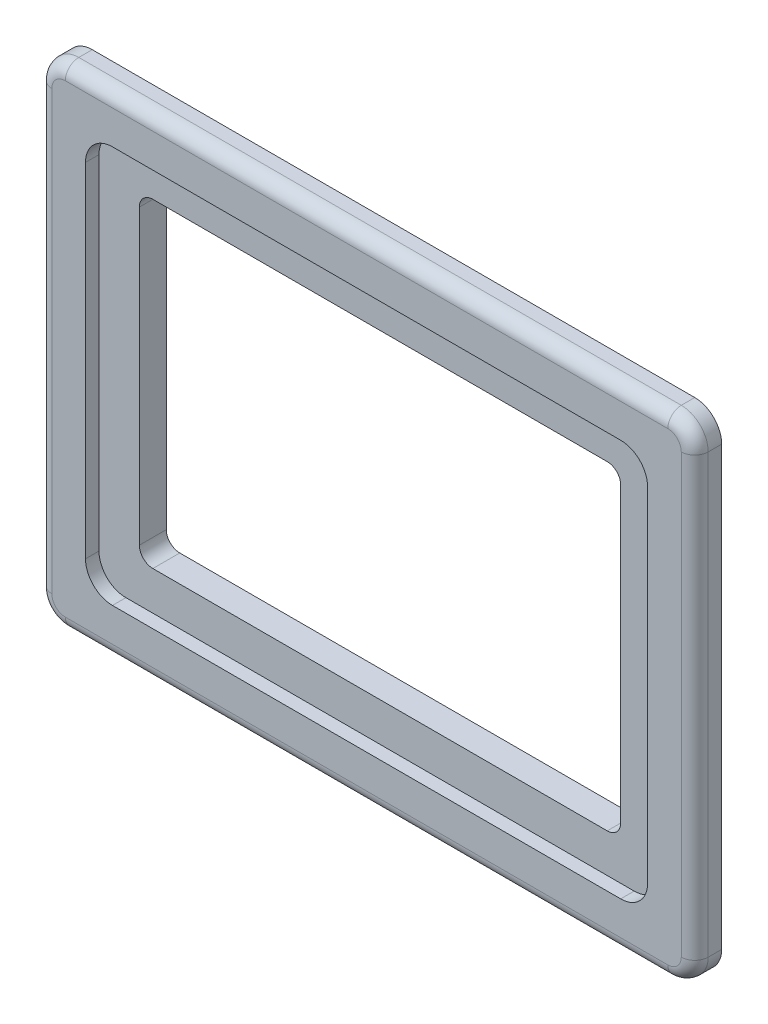
SolidWorks part; units mm, degrees
material "ABS"
ref_plane "Front Plane" through (0, 0, 0) normal (0, 0, 1) x (1, 0, 0)
ref_plane "Top Plane" through (0, 0, 0) normal (0, 1, 0) x (1, 0, 0)
ref_plane "Right Plane" through (0, 0, 0) normal (1, 0, 0) x (0, 0, -1)
sketch "Sketch1" plane through (0, 0, 0) normal (0, 0, 1) x (1, 0, 0)
  line L1 (-154.7812, -115.8875) -> (154.7812, -115.8875)
  line L2 (-154.7812, -115.8875) -> (-154.7812, 115.8875)
  line L3 (-154.7812, 115.8875) -> (154.7812, 115.8875)
  line L4 (154.7812, -115.8875) -> (154.7812, 115.8875)
  line L5 (-154.7812, -115.8875) -> (154.7812, 115.8875) construction
  line L6 (-154.7812, 115.8875) -> (154.7812, -115.8875) construction
  line L11 (-100.7138, -75.4062) -> (100.7138, 75.4063) construction
  line L12 (-100.7138, 75.4063) -> (100.7138, -75.4062) construction
  line L13 (-113.5063, -75.4063) -> (113.5062, -75.4063)
  line L14 (-113.5063, -75.4063) -> (-113.5063, 75.4062)
  line L15 (-113.5063, 75.4062) -> (113.5062, 75.4062)
  line L16 (113.5062, -75.4063) -> (113.5062, 75.4062)
  line L17 (-113.5063, -75.4063) -> (113.5062, 75.4062) construction
  line L18 (-113.5063, 75.4062) -> (113.5062, -75.4063) construction
  line L19 (-132.5562, -93.6625) -> (132.5562, -93.6625)
  line L20 (-132.5562, -93.6625) -> (-132.5562, 93.6625)
  line L21 (-132.5562, 93.6625) -> (132.5562, 93.6625)
  line L22 (132.5562, -93.6625) -> (132.5562, 93.6625)
  line L23 (-132.5562, -93.6625) -> (132.5562, 93.6625) construction
  line L24 (-132.5562, 93.6625) -> (132.5562, -93.6625) construction
  point P0 (0, 0)
  point P6 (0, 0)
  point P11 (0, 0)
  point P16 (0, 0)
  dimension "D1" = 309.5625
  dimension "D2" = 231.775
  dimension "D3" = 227.0125
  dimension "D4" = 150.8125
  dimension "D5" = 265.1125
  dimension "D6" = 187.325
extrude "Boss-Extrude1" add sketch "Sketch1" along normal blind 12.7 contours L1 L4 L3 L2 L22 L19 L20 L21 | L19 L22 L21 L20 L16 L13 L14 L15 region at (-150.9141, 0, 0) region at (-129.3101, 0, 0)
extrude "Boss-Extrude2" add sketch "Sketch1<3>" against normal blind 6.35 contours L19 L22 L21 L20 L16 L13 L14 L15 region at (-129.3101, 0, 0)
sketch "Sketch1<3>" plane through (0, 0, 0) normal (0, 0, 1) x (1, 0, 0) same geometry as "Sketch1"
fillet "Fillet1" radius 12.7 8 edges at (132.5562, -93.6625, -3.175) (132.5562, 93.6625, -3.175) (-132.5562, 93.6625, -3.175) (-132.5562, -93.6625, -3.175) (154.7812, 115.8875, 6.35) (154.7812, -115.8875, 6.35) (-154.7812, 115.8875, 6.35) (-154.7812, -115.8875, 6.35)
extrude "Cut-Extrude1" cut sketch "Sketch1<4>" along direction (0, 0, 1) on the side against the normal blind 6.35 from surface contours L19 L22 L21 L20 L16 L13 L14 L15 region at (-129.3101, 0, 0) starting at face at (0, 0, 12.7)
sketch "Sketch1<4>" plane through (0, 0, 0) normal (0, 0, 1) x (1, 0, 0) same geometry as "Sketch1"
fillet "Fillet2" radius 6.35 4 edges at (113.5062, -75.4063, 0) (-113.5063, -75.4063, 0) (113.5062, 75.4062, 0) (-113.5063, 75.4062, 0)
fillet "Fillet3" radius 12.7 4 edges at (132.5562, 93.6625, 9.525) (132.5562, -93.6625, 9.525) (-132.5562, -93.6625, 9.525) (-132.5562, 93.6625, 9.525)
fillet "Fillet4" radius 6.35 8 edges at (-151.0615, -112.1678, 12.7) (0, -115.8875, 12.7) (151.0615, -112.1678, 12.7) (154.7812, 0, 12.7) (151.0615, 112.1678, 12.7) (0, 115.8875, 12.7) (-151.0615, 112.1678, 12.7) (-154.7812, 0, 12.7)
